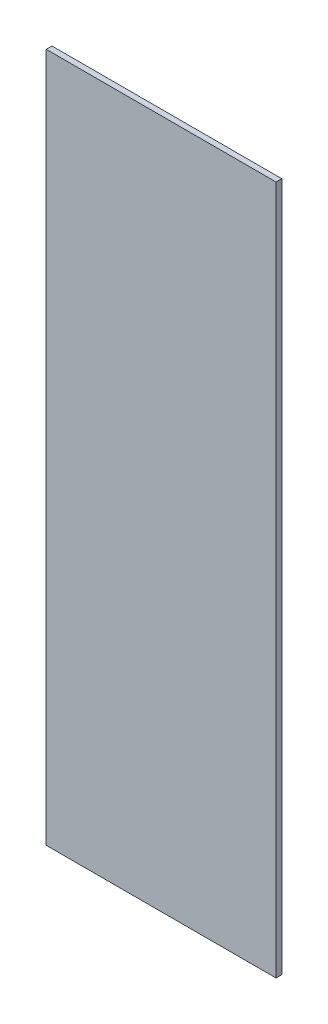
SolidWorks part; units mm, degrees
material "PLA"
ref_plane "Front Plane" through (0, 0, 0) normal (1, 0, 0) x (0, 1, 0)
ref_plane "Top Plane" through (0, 0, 0) normal (0, 0, 1) x (0, 1, 0)
ref_plane "Right Plane" through (0, 0, 0) normal (0, 1, 0) x (-1, 0, 0)
sketch "Sketch1" plane through (0, 0, 0) normal (0, 0, 1) x (0, 1, 0)
  line L1 (-150, -50) -> (150, -50)
  line L2 (-150, -50) -> (-150, 50)
  line L3 (-150, 50) -> (150, 50)
  line L4 (150, -50) -> (150, 50)
  line L5 (-150, -50) -> (150, 50) construction
  line L6 (-150, 50) -> (150, -50) construction
  point P0 (0, 0)
  dimension "D1" = 300
  dimension "D2" = 100
extrude "Boss-Extrude1" add sketch "Sketch1" along normal blind 2.5
equation "\"ball_diameter\"= 3cm"
equation "\"wall_thickness\" = 0.25cm"
equation "\"track_length\" = 25cm"
equation "\"axle\" = 5mm"
equation "\"D1@Sketch1\"=\"track_length\"+5"
equation "\"D1@Boss-Extrude1\"=\"wall_thickness\""
